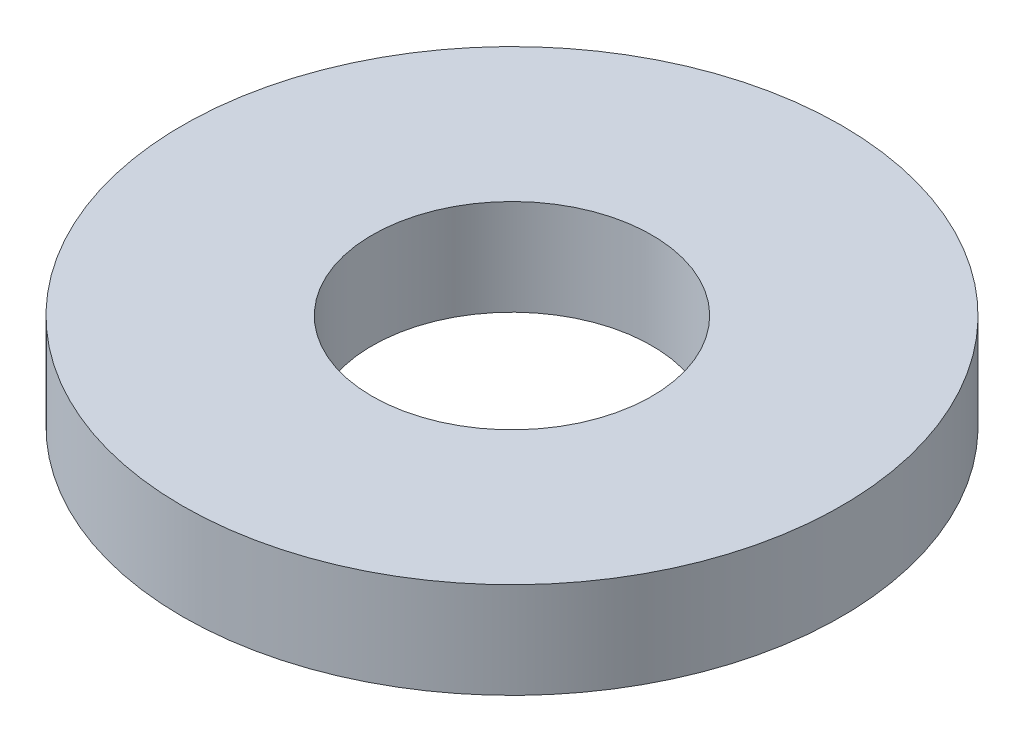
SolidWorks part; units mm, degrees
ref_plane "Front Plane" through (0, 0, 0) normal (0, 0, 1) x (1, 0, 0)
ref_plane "Top Plane" through (0, 0, 0) normal (0, 1, 0) x (1, 0, 0)
ref_plane "Right Plane" through (0, 0, 0) normal (1, 0, 0) x (0, 0, -1)
sketch "Sketch1" plane through (0, 0, 0) normal (0, 1, 0) x (1, 0, 0)
  circle A0 centre (0, 0) radius 82.5
  dimension "FLANGE_OD" = 165
extrude "Boss-Extrude1" add sketch "Sketch1" along normal blind 24
sketch "Sketch2" plane through (0, 0, 0) normal (0, 1, 0) x (1, 0, 0)
  circle A0 centre (0, 0) radius 35
  dimension "BORE_D" = 70
extrude "Cut-Extrude1" cut sketch "Sketch2" along normal through all
sketch "Sketch3" plane through (0, 24, 0) normal (0, 1, 0) x (1, 0, 0)
  circle A0 centre (0, 0) radius 25.6772 construction
  circle A1 centre (-25.6772, 0) radius 7.5711
  dimension "BOLT_D" = 15.1422
  dimension "BOLT_PCD" = 51.3543
extrude "Cut-Extrude2" cut sketch "Sketch3" against normal blind 21.9596 rebuild error yes
pattern_circular "CirPattern1" count 6 over 360 rebuild error yes
